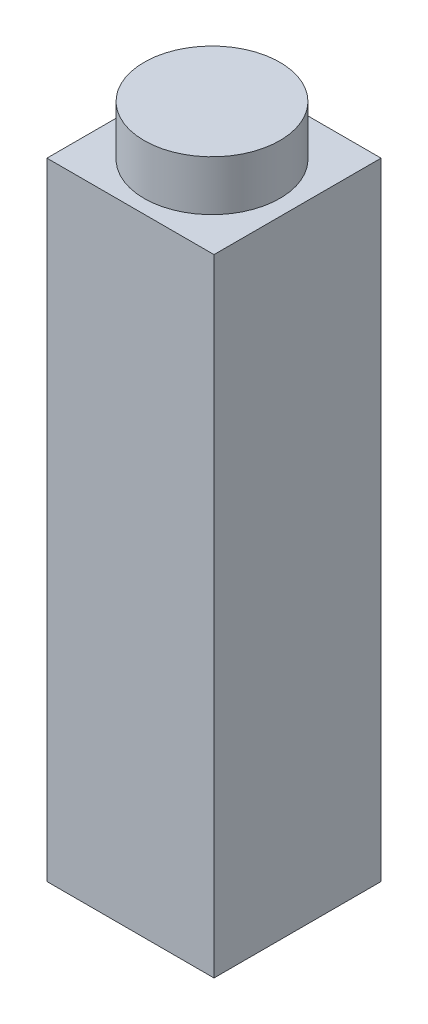
SolidWorks part; units mm, degrees
ref_plane "Front Plane" through (0, 0, 0) normal (0, 0, 1) x (1, 0, 0)
ref_plane "Top Plane" through (0, 0, 0) normal (0, 1, 0) x (1, 0, 0)
ref_plane "Right Plane" through (0, 0, 0) normal (1, 0, 0) x (0, 0, -1)
sketch "Sketch1" plane through (0, 0, 0) normal (0, 1, 0) x (1, 0, 0)
  line L1 (-2, -2) -> (2, -2)
  line L2 (-2, -2) -> (-2, 2)
  line L3 (-2, 2) -> (2, 2)
  line L4 (2, -2) -> (2, 2)
  line L5 (-2, -2) -> (2, 2) construction
  line L6 (-2, 2) -> (2, -2) construction
  point P0 (0, 0)
  dimension "D1" = 4
  dimension "D2" = 4
extrude "Boss-Extrude1" add sketch "Sketch1" along normal blind 15
sketch "Sketch2" plane through (0, 0, 0) normal (0, -1, 0) x (1, 0, 0)
  circle A0 centre (0, 0) radius 1
  dimension "D1" = 2
extrude "Cut-Extrude1" cut sketch "Sketch2" against normal blind 0.5
sketch "Sketch4" plane through (0, 15, 0) normal (0, 1, 0) x (1, 0, 0)
  circle A0 centre (0, -0.0477) radius 1.625
  dimension "D1" = 3.25
extrude "Boss-Extrude2" add sketch "Sketch4" along normal blind 1.2
